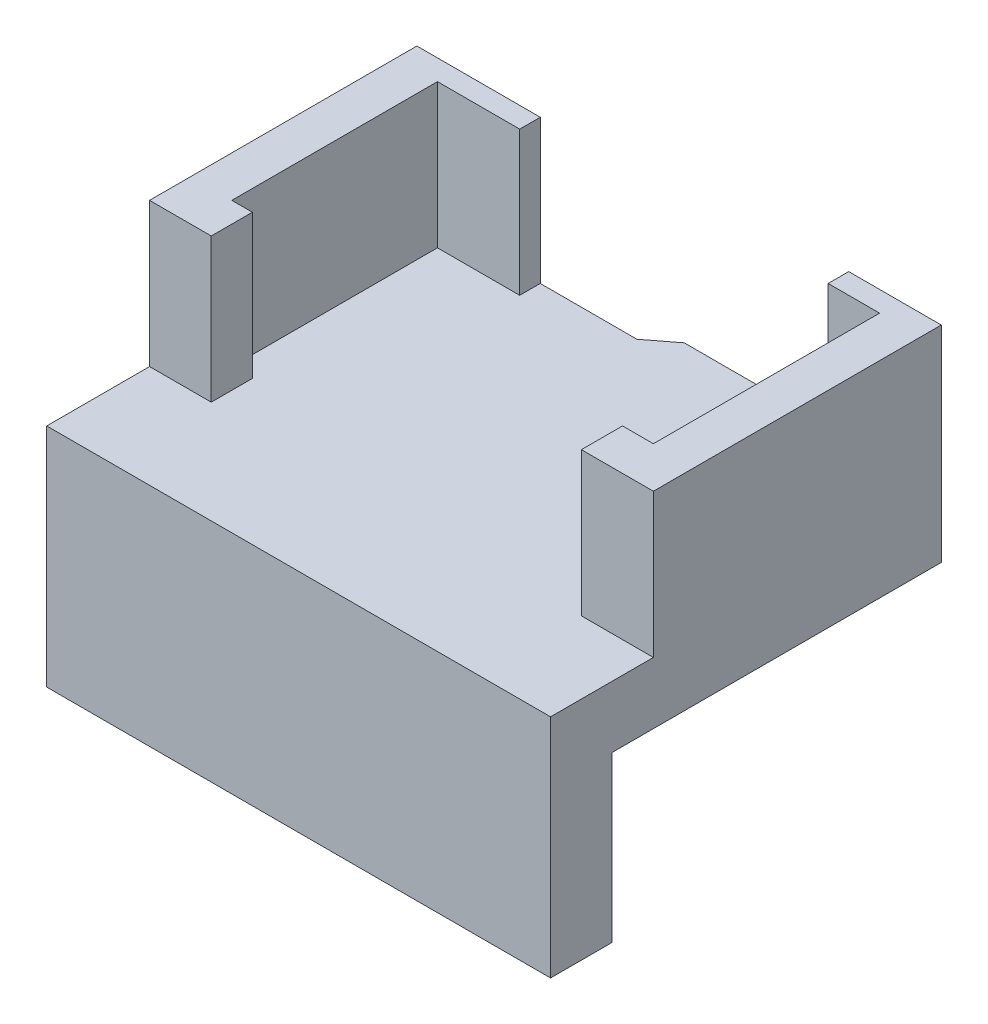
SolidWorks part; units mm, degrees
ref_plane "Front Plane" through (0, 0, 0) normal (0, 0, 1) x (1, 0, 0)
ref_plane "Top Plane" through (0, 0, 0) normal (0, 1, 0) x (1, 0, 0)
ref_plane "Right Plane" through (0, 0, 0) normal (1, 0, 0) x (0, 0, -1)
sketch "Sketch1" plane through (0, 0, 0) normal (0, 1, 0) x (1, 0, 0)
  line L0 (-38.972, -19.2346) -> (-37.972, -19.2346)
  line L1 (-18.972, -19.2346) -> (-18.972, -8.2346)
  line L2 (-38.972, -19.2346) -> (-38.972, -9.2346)
  line L6 (-38.972, -9.2346) -> (-34.972, -9.2346)
  line L7 (-34.972, -9.2346) -> (-34.972, -8.2346)
  line L8 (-34.972, -8.2346) -> (-40.972, -8.2346)
  line L9 (-40.972, -8.2346) -> (-40.972, -21.2346)
  line L10 (-40.972, -21.2346) -> (-37.972, -21.2346)
  line L11 (-37.972, -21.2346) -> (-37.972, -19.2346)
  line L12 (-18.972, -8.2346) -> (-20.972, -8.2346)
  line L13 (-20.972, -8.2346) -> (-20.972, -7.2346)
  line L14 (-20.972, -7.2346) -> (-16.972, -7.2346)
  line L15 (-16.972, -7.2346) -> (-16.972, -21.2346)
  line L16 (-19.972, -19.2346) -> (-18.972, -19.2346)
  line L17 (-16.972, -21.2346) -> (-19.972, -21.2346)
  line L19 (-19.972, -19.2346) -> (-19.972, -21.2346)
extrude "Boss-Extrude1" add sketch "Sketch1" along normal blind 7
sketch "Sketch2" plane through (0, 0, 0) normal (0, -1, 0) x (1, 0, 0)
  line L0 (-40.972, 21.2346) -> (-16.972, 21.2346)
  line L1 (-16.972, 21.2346) -> (-16.972, 7.2346)
  line L2 (-16.972, 21.2346) -> (-16.972, 7.2346) construction
  line L3 (-16.972, 7.2346) -> (-20.972, 7.2346) construction
  line L4 (-16.972, 7.2346) -> (-28.972, 7.2346)
  line L5 (-28.972, 7.2346) -> (-30.2736, 8.2346)
  line L6 (-30.2736, 8.2346) -> (-40.972, 8.2346)
  line L7 (-40.972, 8.2346) -> (-40.972, 21.2346)
extrude "Boss-Extrude2" add sketch "Sketch2" along normal blind 2
sketch "Sketch4" plane through (-16.972, 0, 0) normal (1, 0, 0) x (0, 0, -1)
  line L1 (-7.2346, -2) -> (-21.2346, -2)
  line L2 (-7.2346, -2) -> (-7.2346, 7)
  line L3 (-7.2346, 7) -> (-21.2346, 7)
  line L4 (-21.2346, -2) -> (-21.2346, 7)
extrude "Boss-Extrude3" add sketch "Sketch4" along normal blind 0.5
sketch "Sketch5" plane through (-18.972, 0, 0) normal (-1, 0, 0) x (0, 0, 1)
  line L1 (8.2346, 7) -> (19.2346, 7)
  line L2 (8.2346, 7) -> (8.2346, 0)
  line L3 (8.2346, 0) -> (19.2346, 0)
  line L4 (19.2346, 7) -> (19.2346, 0)
extrude "Cut-Extrude1" cut sketch "Sketch5" against normal blind 0.5
sketch "Sketch6" plane through (0, 0, 21.2346) normal (0, 0, 1) x (1, 0, 0)
  line L0 (-16.472, 7) -> (-16.472, -2) construction
  line L1 (-40.972, -2) -> (-16.472, -2)
  line L2 (-40.972, -2) -> (-40.972, 0)
  line L3 (-40.972, 0) -> (-16.472, 0)
  line L4 (-16.472, -2) -> (-16.472, 0)
extrude "Boss-Extrude4" add sketch "Sketch6" along normal blind 5
sketch "Sketch8" plane through (0, -2, 0) normal (0, -1, 0) x (1, 0, 0)
  line L6 (-40.972, 26.2346) -> (-40.972, 8.2346)
  line L7 (-40.972, 8.2346) -> (-30.2736, 8.2346)
  line L8 (-30.2736, 8.2346) -> (-28.972, 7.2346)
  line L9 (-28.972, 7.2346) -> (-16.472, 7.2346)
  line L10 (-16.472, 7.2346) -> (-16.472, 26.2346)
  line L11 (-16.472, 26.2346) -> (-40.972, 26.2346)
  line L12 (-40.972, 26.2346) -> (-40.972, 8.2346)
  line L13 (-40.972, 8.2346) -> (-30.2736, 8.2346)
  line L14 (-30.2736, 8.2346) -> (-28.972, 7.2346)
  line L15 (-28.972, 7.2346) -> (-16.472, 7.2346)
  line L16 (-16.472, 7.2346) -> (-16.472, 26.2346)
  line L17 (-16.472, 26.2346) -> (-40.972, 26.2346)
  dimension "D1" = 0
extrude "Boss-Extrude6" add sketch "Sketch8" along normal blind 1
sketch "Sketch9" plane through (0, -3, 0) normal (0, -1, 0) x (-1, 0, 0)
  line L1 (16.472, -26.2346) -> (40.972, -26.2346)
  line L2 (16.472, -26.2346) -> (16.472, -23.2346)
  line L3 (16.472, -23.2346) -> (40.972, -23.2346)
  line L4 (40.972, -26.2346) -> (40.972, -23.2346)
  dimension "D1" = 3
extrude "Boss-Extrude7" add sketch "Sketch9" along normal blind 8
